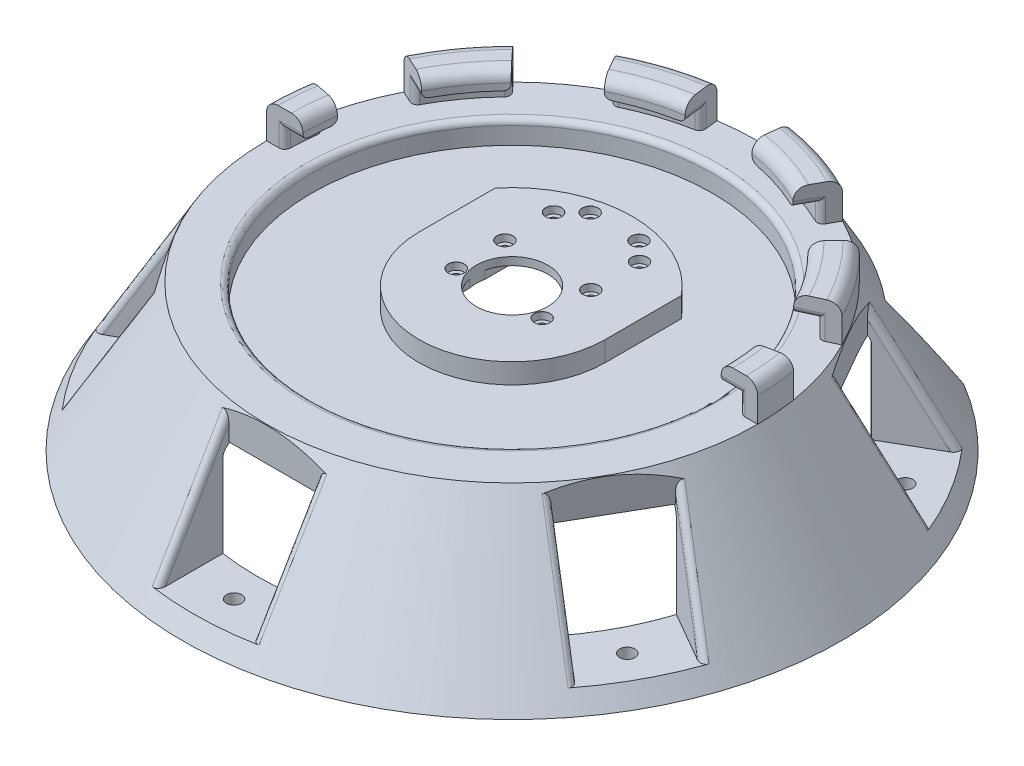
SolidWorks part; units mm, degrees
material "PLA"
ref_plane "Front Plane" through (0, 0, 0) normal (0, 0, 1) x (1, 0, 0)
ref_plane "Top Plane" through (0, 0, 0) normal (0, 1, 0) x (1, 0, 0)
ref_plane "Right Plane" through (0, 0, 0) normal (1, 0, 0) x (0, 0, -1)
sketch "Sketch1" plane through (0, 0, 0) normal (0, 0, 1) x (1, 0, 0)
  line L0 (0, 0) -> (-85.725, 0)
  line L1 (-85.725, 0) -> (-115.0544, -50.8)
  line L2 (-115.0544, -50.8) -> (0, -50.8)
  line L6 (0, 0) -> (0, -50.8) construction
  line L7 (0, 0) -> (0, -50.8)
  dimension "D1" = 85.725
  dimension "D3" = 50.8
  dimension "D4" = 60
revolve "Revolve1" add sketch "Sketch1" angle 360 about L6
sketch "Sketch2" plane through (0, 0, 0) normal (0, 1, 0) x (1, 0, 0)
  circle A0 centre (0, 0) radius 12.5
  dimension "D1" = 25
extrude "Cut-Extrude1" cut sketch "Sketch2" against normal through all
sketch "Sketch3" plane through (0, 0, 0) normal (0, 1, 0) x (1, 0, 0)
  line L0 (-32.5, 0) -> (-32.5, 26.6036)
  line L1 (-32.5, 26.6036) -> (32.5, 26.6036)
  line L2 (32.5, 26.6036) -> (32.5, 0)
  circle A0 centre (0, 0) radius 32.5
  circle A1 centre (0, 0) radius 70
  circle A2 centre (0, 0) radius 42
  circle M1 centre (0, 0) radius 12.5
  dimension "D1" = 65
  dimension "D2" = 140
  dimension "D3" = 84
extrude "Cut-Extrude2" cut sketch "Sketch3" against normal blind 8 contours A1 A0 L0 L1 L2 | A1 A2 region at (0, 0, 33.5845) region at (-68.0201, 0, 0)
sketch "Sketch7" plane through (0, -50.8, 0) normal (0, -1, 0) x (1, 0, 0)
  line L0 (3.6132, 88.8265) -> (-2.6643, -115.0235) construction
  line L1 (-88.0643, 0) -> (82.7357, 0) construction
  line L2 (-62.6643, -63.0586) -> (-62.6643, -115.0235)
  line L3 (-62.6643, -115.0235) -> (57.3357, -115.0235)
  line L4 (57.3357, -115.0235) -> (57.3357, -67.9399)
  arc A2 (57.3357, -67.9399) -> (-62.6643, -63.0586) centre (0, 0) ccw
  circle A3 centre (0, 0) radius 115.0544 construction
  dimension "D1" = 177.8
  dimension "D2" = 25.4
  dimension "D3" = 25.4
  dimension "D4" = 120
  dimension "D5" = 88.9
extrude "Cut-Extrude5" cut sketch "Sketch7" against normal blind 39 contours L3 L4 A2 L2
sketch "Sketch8" plane through (0, 0, 0) normal (0, 1, 0) x (1, 0, 0)
  line L0 (0, 0) -> (3.123, -115.012) construction
  line L2 (-13.0273, -123.925) -> (18.7227, -123.925)
  line L3 (-13.0273, -123.925) -> (-13.0273, -85.825)
  line L4 (-13.0273, -85.825) -> (18.7227, -85.825)
  line L5 (18.7227, -123.925) -> (18.7227, -85.825)
  line L6 (-13.0273, -123.925) -> (18.7227, -85.825) construction
  line L7 (-13.0273, -85.825) -> (18.7227, -123.925) construction
  arc A0 (-62.6643, 96.4919) -> (57.3357, 99.7504) centre (0, 0) ccw construction
  point P6 (2.8477, -104.875)
  dimension "D1" = 85.825
  dimension "D2" = 38.1
  dimension "D3" = 31.75
extrude "Cut-Extrude6" cut sketch "Sketch8" against normal blind 44.45
pattern_circular "CirPattern2" count 6 over 360 about axis through (0, 0, 0) along (0, 1, 0) of "Cut-Extrude6" reverse direction yes
sketch "Sketch9" plane through (0, 0, 0) normal (0, 1, 0) x (1, 0, 0)
  line L0 (0, 0) -> (3.123, -115.012) construction
  arc A0 (-62.6643, 96.4919) -> (57.3357, 99.7504) centre (0, 0) ccw construction
  circle A1 centre (2.7092, -99.772) radius 2.65
  dimension "D1" = 5.3
  dimension "D2" = 15.24
extrude "Cut-Extrude7" cut sketch "Sketch9" against normal through all
pattern_circular "CirPattern3" count 6 over 360 about axis through (0, 0, 0) along (0, 1, 0) of "Cut-Extrude7"
sketch "Sketch12" plane through (0, 0, 0) normal (0, 0, 1) x (1, 0, 0)
  line L0 (85.725, 0) -> (85.725, 12.7)
  line L1 (85.725, 12.7) -> (73.025, 12.7)
  line L2 (73.025, 12.7) -> (73.025, 6.35)
  line L3 (73.025, 6.35) -> (79.375, 6.35)
  line L4 (79.375, 6.35) -> (79.375, 0)
  line L5 (85.725, 0) -> (-85.725, 0) construction
  line L6 (0, 0) -> (0, 12.7) construction
  line L7 (12.5, 0) -> (-12.5, 0) construction
  line L8 (79.375, 0) -> (85.725, 0)
  point P13 (0, 6.35)
  dimension "D1" = 6.35
  dimension "D2" = 73.025
  dimension "D3" = 79.375
  dimension "D4" = 12.7
  dimension "D5" = 12.7
revolve "Revolve2" add sketch "Sketch12" angle 180 about L6
sketch "Sketch15" plane through (0, -11.8, 0) normal (0, -1, 0) x (1, 0, 0)
  line L0 (0, -1000) -> (0, 49000) construction
  point P1 (-15, 4.5)
  point P4 (-15, -12.5)
  point P5 (-15, -29.5)
  point P6 (-8.5, -35.8)
  point P7 (8.5, -35.8)
  point P8 (15, -29.5)
  point P9 (15, -12.5)
  point P10 (15, 4.5)
  dimension "D1" = 17
  dimension "D2" = 17
  dimension "D3" = 4.5
  dimension "D4" = 15
  dimension "D5" = 8.5
  dimension "D6" = 35.8
sketch "Sketch18" plane through (0, 12.7, 0) normal (0, 1, 0) x (1, 0, 0)
  line L0 (46.6433, 89.7185) -> (70.9138, 72.0849)
  line L1 (0, 201000) -> (0, -249000) construction
  line L2 (-15, 100) -> (-9, 50)
  line L3 (-9, 50) -> (9, 50)
  line L4 (9, 50) -> (15, 100)
  line L5 (-15, 100) -> (15, 100)
  line L6 (36.6704, 35.1608) -> (70.9138, 72.0849)
  line L7 (22.1081, 45.7409) -> (36.6704, 35.1608)
  line L8 (46.6433, 89.7185) -> (22.1081, 45.7409)
  line L9 (90.4704, 45.1675) -> (99.7409, 16.6359)
  line L10 (50.334, 6.8913) -> (99.7409, 16.6359)
  line L11 (44.7717, 24.0104) -> (50.334, 6.8913)
  line L12 (90.4704, 45.1675) -> (44.7717, 24.0104)
  line L13 (99.7409, -16.6359) -> (90.4704, -45.1675)
  line L14 (44.7717, -24.0104) -> (90.4704, -45.1675)
  line L15 (50.334, -6.8913) -> (44.7717, -24.0104)
  line L16 (99.7409, -16.6359) -> (50.334, -6.8913)
  line L17 (70.9138, -72.0849) -> (46.6433, -89.7185)
  line L18 (22.1081, -45.7409) -> (46.6433, -89.7185)
  line L19 (36.6704, -35.1608) -> (22.1081, -45.7409)
  line L20 (70.9138, -72.0849) -> (36.6704, -35.1608)
  line L21 (15, -100) -> (-15, -100)
  line L22 (-9, -50) -> (-15, -100)
  line L23 (9, -50) -> (-9, -50)
  line L24 (15, -100) -> (9, -50)
  line L25 (-46.6433, -89.7185) -> (-70.9138, -72.0849)
  line L26 (-36.6704, -35.1608) -> (-70.9138, -72.0849)
  line L27 (-22.1081, -45.7409) -> (-36.6704, -35.1608)
  line L28 (-46.6433, -89.7185) -> (-22.1081, -45.7409)
  line L29 (-90.4704, -45.1675) -> (-99.7409, -16.6359)
  line L30 (-50.334, -6.8913) -> (-99.7409, -16.6359)
  line L31 (-44.7717, -24.0104) -> (-50.334, -6.8913)
  line L32 (-90.4704, -45.1675) -> (-44.7717, -24.0104)
  line L33 (-99.7409, 16.6359) -> (-90.4704, 45.1675)
  line L34 (-44.7717, 24.0104) -> (-90.4704, 45.1675)
  line L35 (-50.334, 6.8913) -> (-44.7717, 24.0104)
  line L36 (-99.7409, 16.6359) -> (-50.334, 6.8913)
  line L37 (-70.9138, 72.0849) -> (-46.6433, 89.7185)
  line L38 (-22.1081, 45.7409) -> (-46.6433, 89.7185)
  line L39 (-36.6704, 35.1608) -> (-22.1081, 45.7409)
  line L40 (-70.9138, 72.0849) -> (-36.6704, 35.1608)
  point P4 (0, 50)
  point P7 (0, 100)
  point P48 (0, 0)
  dimension "D1" = 18
  dimension "D2" = 50
  dimension "D3" = 30
  dimension "D4" = 50
  dimension "D5" = 10
extrude "Cut-Extrude9" cut sketch "Sketch18" against normal blind 12.7
sketch "Sketch20" plane through (0, -11.8, 0) normal (0, -1, 0) x (1, 0, 0)
  line L0 (-22.5, -33) -> (-12.5, -40)
  line L1 (22.5, 20) -> (-22.5, 20)
  line L2 (22.5, 20) -> (22.5, -40)
  line L3 (22.5, -40) -> (-22.5, -40)
  line L4 (-22.5, 20) -> (-22.5, -40)
  line L5 (22.5, 20) -> (-22.5, -40) construction
  line L6 (22.5, -40) -> (-22.5, 20) construction
  line L7 (-12.5, -40) -> (12.5, -40)
  line L8 (12.5, -40) -> (22.5, -33)
  point P0 (0, -10)
  line M11 (-13.0268, 13) -> (13.0268, 13)
  line M12 (13.0268, 13) -> (13.0268, -34)
  line M13 (13.0268, -34) -> (-13.0268, -34)
  line M14 (-13.0268, -34) -> (-13.0268, 13)
  dimension "D1" = 60
  dimension "D2" = 45
  dimension "D3" = 10
  dimension "D4" = 10
  dimension "D5" = 7
  dimension "D6" = 7
  dimension "D7" = 10
extrude "Cut-Extrude11" cut sketch "Sketch3<3>" against normal blind 1 contours A0 L1 M1 | A0 L1 L0 | L1 A0 | L1 A2 A0 | A0 L2 L1 | A0 region at (-28.056, 0, -14.587) region at (-28.5629, 0, -20.2686) region at (0, 0, -33.9353) region at (28.5629, 0, -20.2686) region at (0, 0, -28.9815)
sketch "Sketch3<3>" plane through (0, 0, 0) normal (0, 1, 0) x (1, 0, 0) same geometry as "Sketch3"
sketch "Sketch22" plane through (0, -1, 0) normal (0, 1, 0) x (1, 0, 0)
  circle A0 centre (-15, 12.5) radius 1.4
  circle A1 centre (-15, 29.5) radius 1.4
  circle A2 centre (-8.5, 35.8) radius 1.4
  circle A3 centre (8.5, 35.8) radius 1.4
  circle A4 centre (15, 29.5) radius 1.4
  circle A5 centre (15, 12.5) radius 1.4
  circle A6 centre (15, -4.5) radius 1.4
  circle A7 centre (-15, -4.5) radius 1.4
hole_wizard "CBORE for M2.5 SHCS1" positions "Sketch23" profile "Sketch24" counterbore size "M2.5" standard "ANSI Metric" end condition through all
sketch "Sketch23" plane through (0, -1, 0) normal (0, 1, 0) x (1, 0, 0)
  point P0 (-15, -4.5)
  point P3 (-15, 12.5)
  point P6 (-15, 29.5)
  point P9 (-8.5, 35.8)
  point P12 (8.5, 35.8)
  point P15 (15, 29.5)
  point P18 (15, 12.5)
  point P21 (15, -4.5)
sketch "Sketch24" plane through (-15, -1, 4.5) normal (1, 0, 0) x (0, 0, 1)
  line L0 (0, 0) -> (0, 49.8)
  line L1 (0, 49.8) -> (1.45, 49.8)
  line L3 (1.45, 49.8) -> (1.45, 2.5)
  line L4 (2.75, 2.5) -> (1.45, 2.5)
  line L5 (2.75, 2.5) -> (2.75, 0.025)
  line L6 (2.75, 0.025) -> (2.775, 0)
  line L7 (2.775, 0) -> (0, 0)
  line L8 (-2.75, 0.025) -> (-2.775, 0) construction
  line L11 (0, -6.35) -> (0, 107.95) construction
  dimension "Thru Hole Dia." = 2.9
  dimension "Thru Hole Depth" = 49.8
  dimension "C'Bore Dia." = 5.5
  dimension "C'Bore Depth" = 2.5
  dimension "Near C'Sink Dia." = 5.55
  dimension "Near C'Sink Angle" = 90
fillet "Fillet1" radius 4 12 edges at (85.4509, 12.7, -6.8497) (69.353, 12.7, -50.3879) (26.4905, 12.7, -81.5293) (-26.4905, 12.7, -81.5293) (-69.353, 12.7, -50.3879) (-85.4509, 12.7, -6.8497) (-72.8088, 12.7, -5.6148) (-59.0785, 12.7, -42.923) (-22.566, 12.7, -69.4509) (22.566, 12.7, -69.4509) (59.0785, 12.7, -42.923) (72.8088, 12.7, -5.6148)
fillet "Fillet2" radius 2 12 edges at (75.2789, 6.35, -11.8112) (76.2, 6.35, 0) (53.9595, 6.35, -53.8033) (67.8444, 6.35, -34.6924) (12.0293, 6.35, -75.2444) (34.4956, 6.35, -67.9447) (-12.0293, 6.35, -75.2444) (-34.4956, 6.35, -67.9447) (-53.9595, 6.35, -53.8033) (-67.8444, 6.35, -34.6924) (-75.2789, 6.35, -11.8112) (-76.2, 6.35, 0)
fillet "Fillet3" radius 2 12 edges at (-78.3963, 4.175, -12.4261) (-56.1201, 4.175, -56.1331) (-70.7278, 4.175, -36.0273) (-12.4079, 4.175, -78.3992) (56.1201, 4.175, -56.1331) (78.3963, 4.175, -12.4261) (-79.375, 4.175, 0) (-36.0437, 4.175, -70.7195) (12.4079, 4.175, -78.3992) (36.0437, 4.175, -70.7195) (70.7278, 4.175, -36.0273) (79.375, 4.175, 0)
fillet "Fillet4" radius 2 10 edges
fillet "Fillet5" radius 2 1 edges at (0, 0, 70)
fillet "Fillet6" radius 4 4 edges at (88.8529, -11.8, -2.8943) (-88.8529, -11.8, 2.8943) (-41.9199, -11.8, 78.396) (46.933, -11.8, 75.5017)
fillet "Fillet7" radius 4 1 edges at (61.7573, -11.8, -63.9472)
fillet "Fillet8" radius 4 1 edges at (-66.2697, -11.8, -59.2583)
fillet "Fillet9" radius 1 2 edges
sketch "Sketch28" plane through (0, -11.8, 0) normal (0, -1, 0) x (1, 0, 0)
  line L0 (9.2, 12) -> (-9.2, 12)
  line L1 (-12.2, 9) -> (-12.2, -30)
  line L2 (-9.2, -33) -> (9.2, -33)
  line L3 (12.2, -30) -> (12.2, 9)
  arc A0 (-9.2, 12) -> (-12.2, 9) centre (-9.2, 9) ccw
  arc A1 (-12.2, -30) -> (-9.2, -33) centre (-9.2, -30) ccw
  arc A2 (9.2, -33) -> (12.2, -30) centre (9.2, -30) ccw
  arc A3 (12.2, 9) -> (9.2, 12) centre (9.2, 9) ccw
extrude "Cut-Extrude12" cut sketch "Sketch28" against normal offset from surface (8.05 mm away) 2.75 up to face at (-15, -1, 7.275)
extrude "Cut-Extrude15" cut sketch "Sketch20" against normal offset from surface (5.3 mm away) 2.75 contours L3 L8 L2 L1 L4 L0 M14 M11 M12 M13 | M11 M14 M13 M12 region at (-21.75, -11.8, -6.5) region at (0, -11.8, -10.5) up to face at (0, -3.75, -23.7441)
